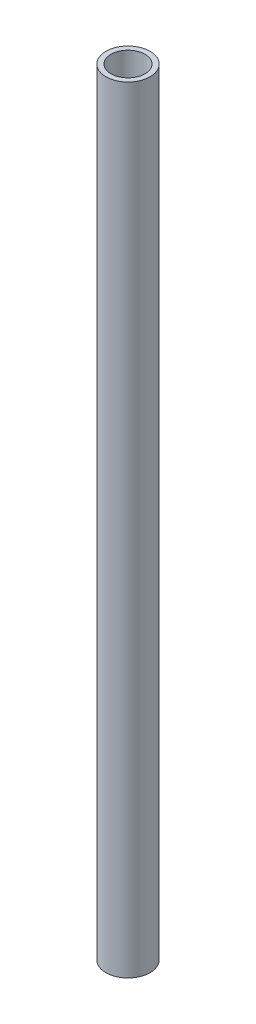
SolidWorks part; units mm, degrees
ref_plane "Płaszczyzna przednia" through (0, 0, 0) normal (0, 0, 1) x (1, 0, 0)
ref_plane "Płaszczyzna górna" through (0, 0, 0) normal (0, 1, 0) x (1, 0, 0)
ref_plane "Płaszczyzna prawa" through (0, 0, 0) normal (1, 0, 0) x (0, 0, -1)
sketch "Sketch1" plane through (0, 0, 0) normal (0, 1, 0) x (1, 0, 0)
  circle A0 centre (0, 0) radius 6.5
  circle A1 centre (0, 0) radius 3.5
  dimension "D1" = 3
  dimension "D2" = 7
extrude "Boss-Extrude1" add sketch "Sketch1" along normal blind 228.4
sketch "Sketch2" plane through (0, 228.4, 0) normal (0, 1, 0) x (1, 0, 0)
  circle A1 centre (0, 0) radius 5
  dimension "D1" = 10
extrude "Cut-Extrude1" cut sketch "Sketch2" against normal blind 31
extrude "Cut-Extrude2" cut sketch "Sketch2<2>" along normal blind 31 from surface starting at face at (0, 0, 6.5)
sketch "Sketch2<2>" plane through (0, 228.4, 0) normal (0, 1, 0) x (1, 0, 0) same geometry as "Sketch2"
equation "\"G\"= 3'grubość ścianki"
equation "\"L\"= 300'długość całkowita"
equation "\"G1\"= 31'głębokość gwintu"
